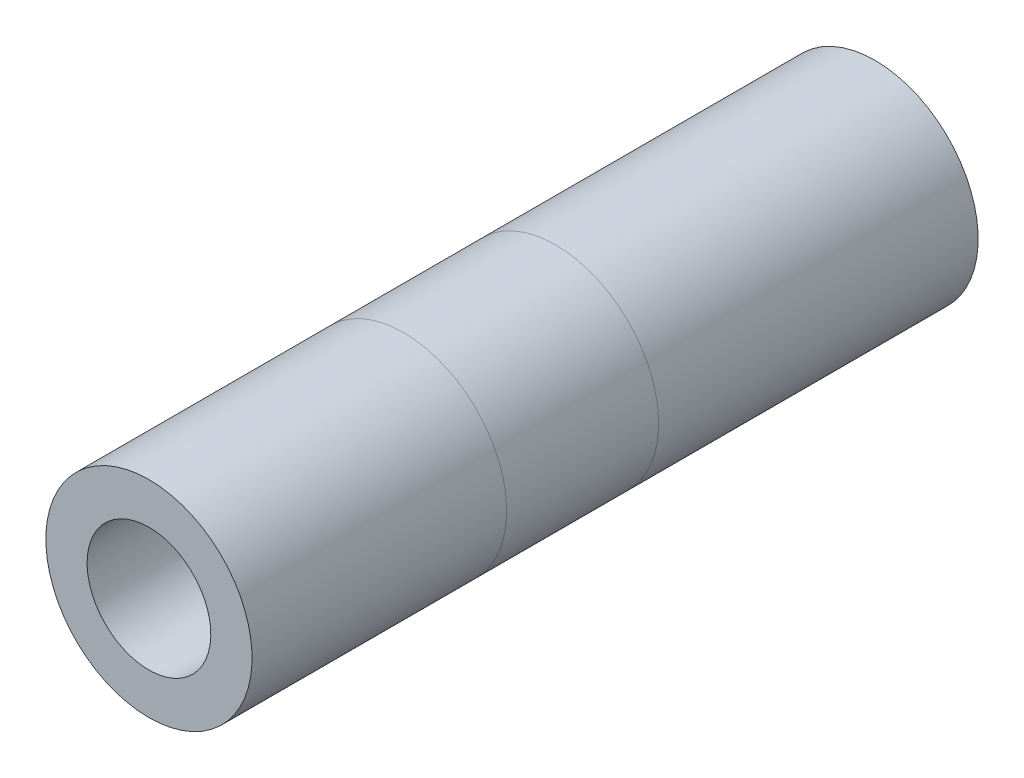
SolidWorks part; units mm, degrees
material "Silicon Rubber"
ref_plane "X-Y Datum" through (0, 0, 0) normal (0, 0, 1) x (1, 0, 0)
ref_plane "X-Z Datum" through (0, 0, 0) normal (0, 1, 0) x (1, 0, 0)
ref_plane "Y-Z Datum" through (0, 0, 0) normal (1, 0, 0) x (0, 0, -1)
sketch3d "3DSketch1"
  line L0 (-46.03, 0, -24.6) -> (-46.03, 0, 0)
  line L1 (-46.03, 0, 0) -> (-46.03, 0, 11.7)
  line L2 (-46.03, 0, 31.3016) -> (-46.03, 0, 11.7)
  arc A0 (-42.0547, 0, 0) -> (-50.0053, 0, 0) centre (-46.03, 0, 0) ccw construction
  arc A1 (-42.0547, 0, 0) -> (-50.0053, 0, 0) centre (-46.03, 0, 0) ccw construction
  arc A2 (-46.03, 5, -24.6) -> (-41.03, 0, -24.6) centre (-46.03, 0, -24.6) ccw construction
  arc A3 (-46.03, 5, -24.6) -> (-41.03, 0, -24.6) centre (-46.03, 0, -24.6) ccw construction
  circle A4 centre (-46.03, 0, 11.7) radius 6.1071 construction
  circle A5 centre (-46.03, 0, 11.7) radius 6.1071 construction
  circle A6 centre (-46.03, 0, 31.3016) radius 6.5 construction
  circle A7 centre (-46.03, 0, 31.3016) radius 6.5 construction
  point P3 (-46.03, 0, 3.9753)
  point P4 (-46.03, 0, 3.9753)
  point P8 (-46.03, 0, -29.6)
  point P9 (-46.03, 0, -29.6)
  point P12 (-46.03, 0, 5.593)
  point P14 (-46.03, 0, 5.593)
  point P17 (-46.03, 0, 24.8016)
  point P19 (-46.03, 0, 24.8016)
sweep "Sweep1" add path "3DSketch1" circular profile diameter 15.875 parameters "D3"=15.875
sweep "Cut-Sweep1" cut path "3DSketch1<2>" circular profile diameter 9.525 parameters "D3"=9.525
sketch3d "3DSketch1<2>" same geometry as "3DSketch1"
